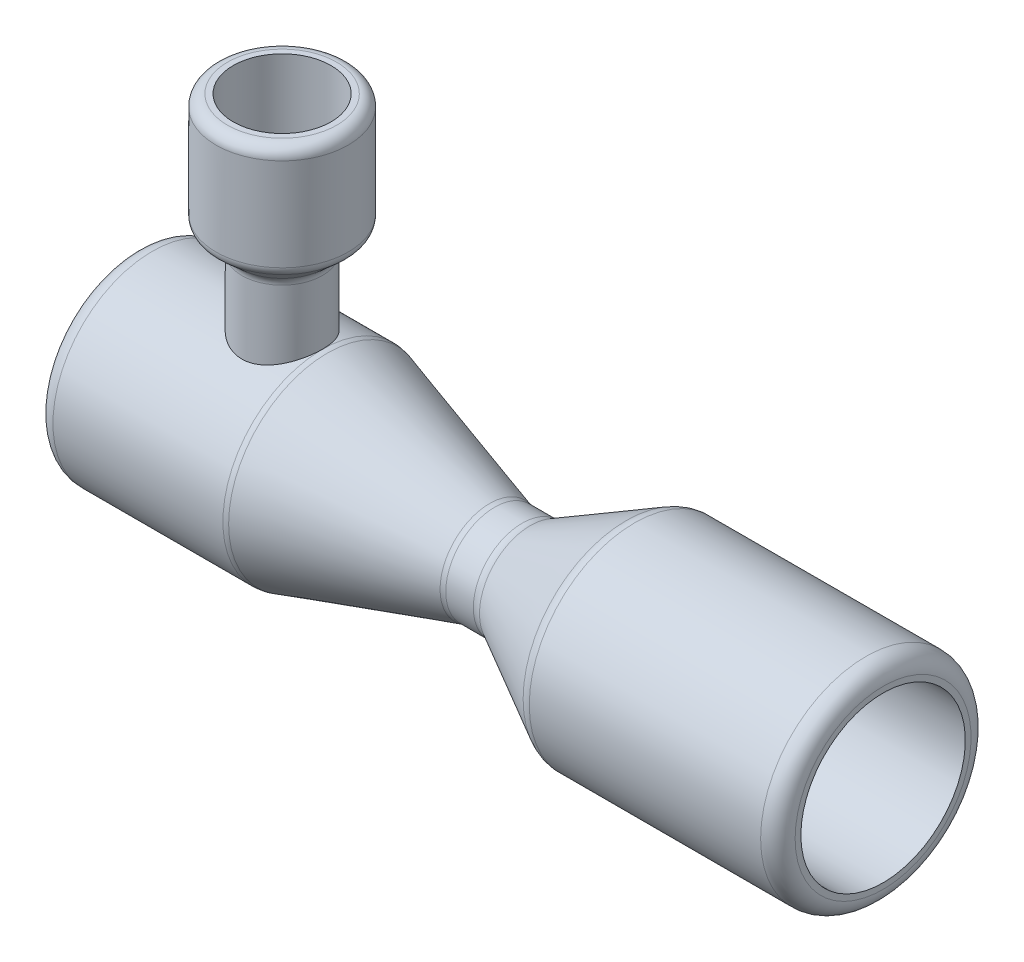
SolidWorks part; units mm, degrees
ref_plane "Alzado" through (0, 0, 0) normal (0, 0, 1) x (1, 0, 0)
ref_plane "Planta" through (0, 0, 0) normal (0, 1, 0) x (1, 0, 0)
ref_plane "Vista lateral" through (0, 0, 0) normal (1, 0, 0) x (0, 0, -1)
sketch "Croquis1" plane through (0, 0, 0) normal (0, 0, 1) x (1, 0, 0)
  line L0 (0, 0) -> (153.2541, 0) construction
  line L2 (0, 2.15) -> (6.263, 2.15)
  line L3 (0, 2.15) -> (0, 8.65)
  line L6 (11, 6.65) -> (16.5, 6.65)
  line L10 (31.64, 2.25) -> (32.7648, 2.25)
  line L12 (31.0376, 4.25) -> (34.0376, 4.25)
  line L18 (6.7359, 2.1276) -> (16.3946, 1.21)
  line L19 (16.6058, 1.1945) -> (20.2895, 1.0014)
  line L20 (20.5, 1.2011) -> (20.5, 1.8218)
  line L21 (20.3338, 2.0189) -> (10.8308, 3.65)
  line L23 (10, 4.6356) -> (10, 5.65)
  line L24 (0, 8.65) -> (16.5, 8.65)
  line L25 (16.5, 8.65) -> (31.0376, 4.25)
  line L26 (22.0376, 4.4503) -> (30.4526, 2.393)
  line L27 (35.1556, 2.8587) -> (41.9197, 6.5413)
  line L28 (44.3105, 7.15) -> (65.0376, 7.15)
  line L29 (34.0376, 4.25) -> (43.0376, 9.15)
  line L30 (43.0376, 9.15) -> (65.0376, 9.15)
  line L31 (65.0376, 9.15) -> (65.0376, 7.15)
  arc A1 (6.7359, 2.1276) -> (6.263, 2.15) centre (6.263, -2.85) ccw
  arc A2 (16.6058, 1.1945) -> (16.3946, 1.21) centre (16.8674, 6.1876) cw
  arc A3 (10.8308, 3.65) -> (10, 4.6356) centre (11, 4.6356) cw
  arc A4 (10, 5.65) -> (11, 6.65) centre (11, 5.65) cw
  arc A5 (20.2895, 1.0014) -> (20.5, 1.2011) centre (20.3, 1.2011) ccw
  arc A6 (20.5, 1.8218) -> (20.3338, 2.0189) centre (20.3, 1.8218) ccw
  arc A8 (16.5, 6.65) -> (19.5, 5.65) centre (16.5, 1.65) cw
  arc A9 (19.5, 5.65) -> (22.0376, 4.4503) centre (23.7, 11.25) ccw
  arc A10 (44.3105, 7.15) -> (41.9197, 6.5413) centre (44.3105, 2.15) ccw
  arc A11 (32.7648, 2.25) -> (35.1556, 2.8587) centre (32.7648, 7.25) ccw
  arc A12 (31.64, 2.25) -> (30.4526, 2.393) centre (31.64, 7.25) cw
  point P27 (6.5, 2.15)
  point P30 (16.5, 1.2)
  point P35 (20.5, 0.9904)
  point P38 (20.5, 1.9904)
  point P40 (0, 0)
  point P43 (43.0376, 7.15)
  point P47 (34.0376, 2.25)
  point P50 (31.0376, 2.25)
  dimension "D8" = 5
  dimension "D9" = 5
  dimension "D11" = 1
  dimension "D12" = 0.2
  dimension "D18" = 5
  dimension "D19" = 7
  dimension "D28" = 5
  dimension "D1" = 2.15
  dimension "D2" = 6.5
  dimension "D4" = 3
  dimension "D3" = 1.2
  dimension "D7" = 10
  dimension "D5" = 4
  dimension "D10" = 1
  dimension "D13" = 6.5
  dimension "D14" = 10
  dimension "D6" = 4
  dimension "D15" = 3
  dimension "D21" = 3
  dimension "D16" = 2.25
  dimension "D20" = 9
  dimension "D17" = 2
  dimension "D22" = 2
  dimension "D23" = 3
  dimension "D24" = 14.3
  dimension "D25" = 9
  dimension "D26" = 22
  dimension "D27" = 2
revolve "Revolución1" add sketch "Croquis1" angle 360 about L0
fillet "Redondeo1" radius 1.5 7 edges at (65.0376, 0, 9.15) (43.0376, 0, 9.15) (34.0376, 0, 4.25) (31.0376, 0, 4.25) (16.5, 0, 8.65) (0, 0, 2.15) (0, 0, 8.65)
ref_plane "Plano1" through (0, 8.65, 0) normal (0, 1, 0) x (1, 0, 0)
sketch "Croquis2" plane through (0, 8.65, 0) normal (0, 1, 0) x (1, 0, 0)
  line L0 (16.278, 8.65) -> (16.278, -8.65) construction
  circle A0 centre (12.778, 0) radius 3.5
  circle A1 centre (12.778, 0) radius 2
  dimension "D1" = 7
  dimension "D2" = 4
extrude "Saliente-Extruir1" add sketch "Croquis2" along normal blind 6 and the other way up to surface separate body other way up to face at (16.278, 0, -8.65)
sketch "Croquis3" plane through (0, 8.65, 0) normal (0, 1, 0) x (1, 0, 0)
  circle A0 centre (12.778, 0) radius 2 construction
  circle A1 centre (12.778, 0) radius 2
extrude "Cortar-Extruir2" cut sketch "Croquis3" against normal blind 4
fillet "Redondeo2" radius 1 2 edges at (10.8037, 6.6228, -0.3195) (14.7778, 6.6499, -0.0289)
sketch "Croquis4" plane through (0, 14.65, 0) normal (0, 1, 0) x (1, 0, 0)
  circle A0 centre (12.778, 0) radius 5.75
  circle A1 centre (12.778, 0) radius 4.25
  dimension "D1" = 11.5
  dimension "D2" = 1.5
extrude "Saliente-Extruir2" add sketch "Croquis4" along normal blind 9.5 from offset 2 separate body
sketch "Croquis5" plane through (0, 0, 0) normal (0, 0, 1) x (1, 0, 0)
  line L2 (7.028, 16.65) -> (8.528, 16.65)
  line L3 (9.278, 14.65) -> (10.778, 14.65)
  line L4 (8.528, 16.65) -> (10.778, 14.65)
  line L5 (9.278, 14.65) -> (7.028, 16.65)
sweep "Barrer2" add profiles "Croquis5" path edge at (12.778, 16.65, 4.25) parameters "D4"=0
fillet "Redondeo3" radius 1 5 edges at (12.778, 14.65, 3.5) (12.778, 16.65, 5.75) (12.778, 26.15, 5.75) (8.528, 16.65, 0) (10.778, 14.65, 0)
equation "\"Entrada\"=2.15"
equation "\"D1@Croquis1\"=\"Entrada\""
